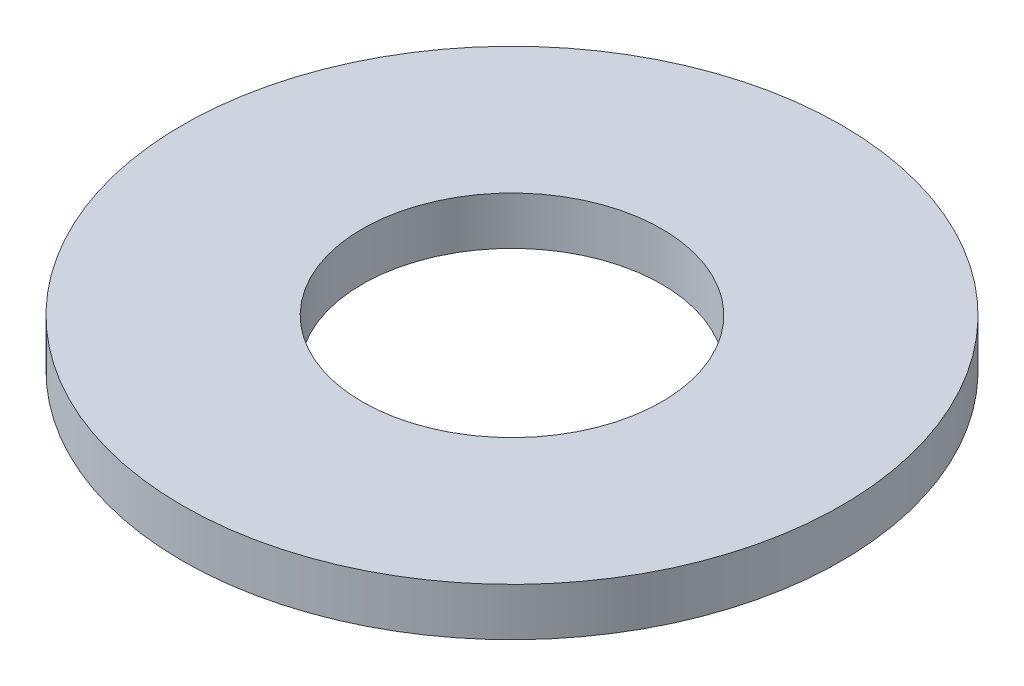
SolidWorks part; units mm, degrees
ref_plane "Front Plane" through (0, 0, 0) normal (0, 0, 1) x (1, 0, 0)
ref_plane "Top Plane" through (0, 0, 0) normal (0, 1, 0) x (1, 0, 0)
ref_plane "Right Plane" through (0, 0, 0) normal (1, 0, 0) x (0, 0, -1)
sketch "Sketch1" plane through (0, 0, 0) normal (0, 1, 0) x (1, 0, 0)
  circle A0 centre (0, 0) radius 82.5
  dimension "FLANGE_OD" = 165
extrude "Boss-Extrude1" add sketch "Sketch1" along normal blind 12
sketch "Sketch2" plane through (0, 0, 0) normal (0, 1, 0) x (1, 0, 0)
  circle A0 centre (0, 0) radius 37.5
  dimension "BORE_D" = 75
extrude "Cut-Extrude1" cut sketch "Sketch2" along normal through all
sketch "Sketch3" plane through (0, 12, 0) normal (0, 1, 0) x (1, 0, 0)
  circle A0 centre (0, 0) radius 24.2345 construction
  circle A1 centre (-24.2345, 0) radius 5.6777
  dimension "BOLT_D" = 11.3555
  dimension "BOLT_PCD" = 48.469
extrude "Cut-Extrude2" cut sketch "Sketch3" against normal blind 7.853 rebuild error yes
pattern_circular "CirPattern1" count 6 over 360 rebuild error yes
